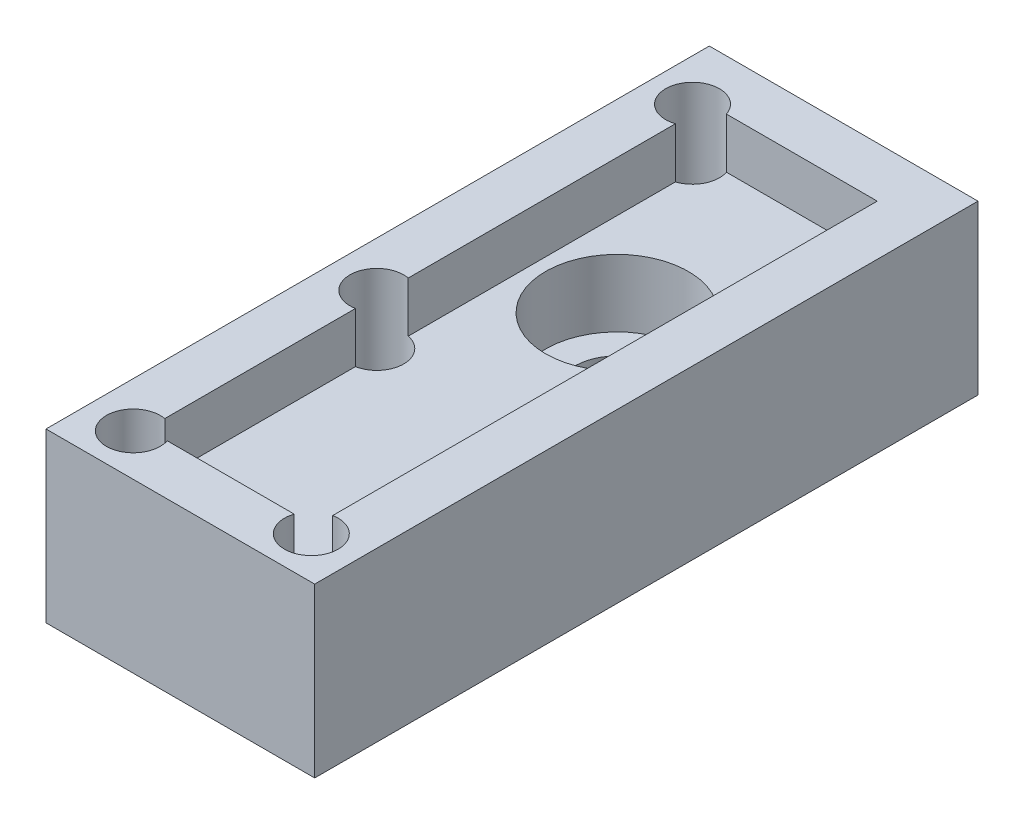
SolidWorks part; units mm, degrees
ref_plane "Front Plane" through (0, 0, 0) normal (0, 0, 1) x (1, 0, 0)
ref_plane "Top Plane" through (0, 0, 0) normal (0, 1, 0) x (1, 0, 0)
ref_plane "Right Plane" through (0, 0, 0) normal (1, 0, 0) x (0, 0, -1)
sketch "Sketch1" plane through (0, 0, 0) normal (0, 1, 0) x (1, 0, 0)
  line L1 (0, 0) -> (16, 0)
  line L2 (0, 0) -> (0, 39.5)
  line L3 (0, 39.5) -> (16, 39.5)
  line L4 (16, 0) -> (16, 39.5)
extrude "Boss-Extrude1" add sketch "Sketch1" along normal blind 15
sketch "Sketch2" plane through (0, 15, 0) normal (0, 1, 0) x (1, 0, 0)
  line L1 (3, 3) -> (13, 3)
  line L2 (3, 3) -> (3, 36.5)
  line L3 (3, 36.5) -> (13, 36.5)
  line L4 (13, 3) -> (13, 36.5)
extrude "Cut-Extrude1" cut sketch "Sketch2" against normal blind 3
sketch "Sketch3" plane through (0, 12, 0) normal (0, 1, 0) x (1, 0, 0)
  circle A0 centre (2.7, 2.5) radius 1.6
extrude "Cut-Extrude2" cut sketch "Sketch3" against normal through all and the other way through all
sketch "Sketch4" plane through (0, 15, 0) normal (0, 1, 0) x (1, 0, 0)
  circle A0 centre (13.3, 2.5) radius 1.6
  circle A1 centre (2.7, 17) radius 1.6
  circle A2 centre (2.5, 36) radius 1.6
extrude "Cut-Extrude3" cut sketch "Sketch4" against normal through all and the other way blind 3
sketch "Sketch5" plane through (0, 12, 0) normal (0, 1, 0) x (1, 0, 0)
  circle A0 centre (8, 26) radius 2.5
sketch "Sketch8" plane through (0, 12, 0) normal (0, 1, 0) x (1, 0, 0)
  circle A0 centre (8, 26) radius 4.25
extrude "Cut-Extrude4" cut sketch "Sketch5" against normal blind 20
extrude "Cut-Extrude5" cut sketch "Sketch8" against normal blind 4 contours A0
sketch "Sketch9" plane through (0, 0, 0) normal (0, -1, 0) x (1, 0, 0)
  line L1 (-3.9867, 7.4491) -> (19.0874, 7.4491)
  line L2 (-3.9867, 7.4491) -> (-3.9867, -42.1704)
  line L3 (-3.9867, -42.1704) -> (19.0874, -42.1704)
  line L4 (19.0874, 7.4491) -> (19.0874, -42.1704)
extrude "Cut-Extrude6" cut sketch "Sketch9" against normal blind 5
